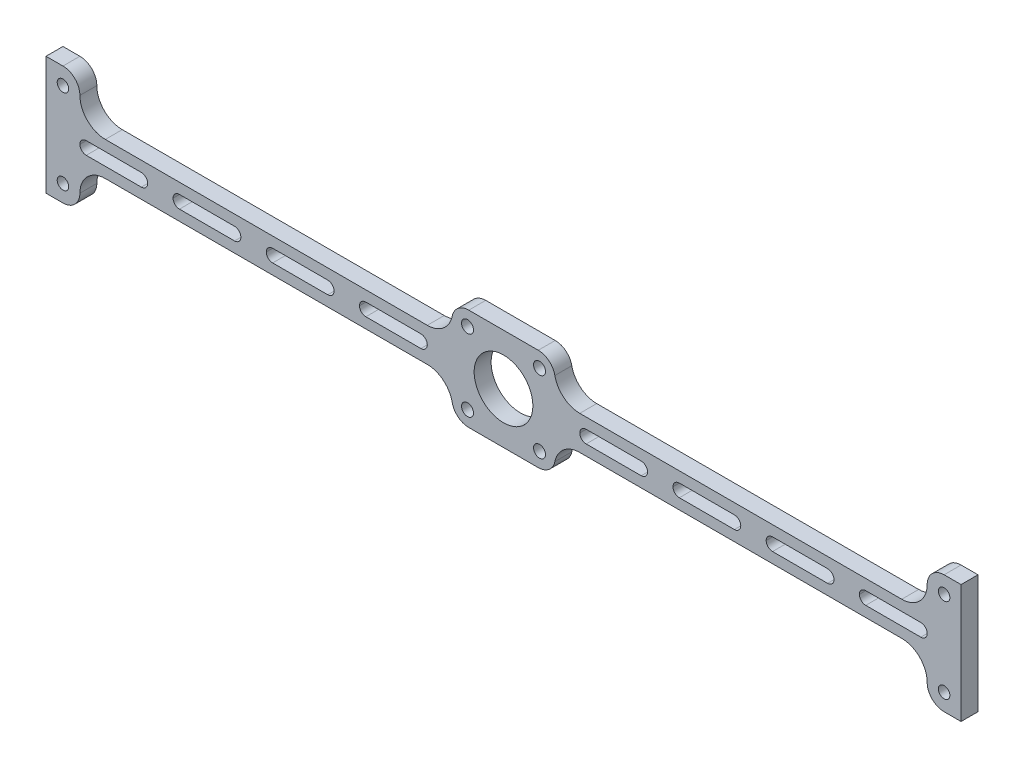
SolidWorks part; units mm, degrees
material "6061-T6 (SS)"
ref_plane "Front" through (0, 0, 0) normal (0, 0, 1) x (1, 0, 0)
ref_plane "Top" through (0, 0, 0) normal (0, 1, 0) x (1, 0, 0)
ref_plane "Right" through (0, 0, 0) normal (1, 0, 0) x (0, 0, -1)
sketch "Sketch4" plane through (0, 0, 0) normal (0, 0, 1) x (1, 0, 0)
  line L0 (-165.1, 0) -> (0, 0) construction
  line L1 (-158.75, -6.35) -> (158.75, -6.35)
  line L2 (-158.75, -6.35) -> (-158.75, 6.35)
  line L3 (-158.75, 6.35) -> (158.75, 6.35)
  line L4 (158.75, -6.35) -> (158.75, 6.35)
  line L5 (-158.75, -6.35) -> (158.75, 6.35) construction
  line L6 (-158.75, 6.35) -> (158.75, -6.35) construction
  line L7 (-171.45, -22.225) -> (-158.75, -22.225)
  line L8 (-171.45, -22.225) -> (-171.45, 22.225)
  line L9 (-171.45, 22.225) -> (-158.75, 22.225)
  line L10 (-158.75, -22.225) -> (-158.75, 22.225)
  line L11 (-171.45, -22.225) -> (-158.75, 22.225) construction
  line L12 (-171.45, 22.225) -> (-158.75, -22.225) construction
  line L17 (171.45, 22.225) -> (158.75, 22.225)
  line L18 (171.45, 22.225) -> (171.45, -22.225)
  line L19 (171.45, -22.225) -> (158.75, -22.225)
  line L20 (158.75, 22.225) -> (158.75, -22.225)
  line L21 (171.45, 22.225) -> (158.75, -22.225) construction
  line L22 (171.45, -22.225) -> (158.75, 22.225) construction
  line L23 (0, 0) -> (165.1, 0) construction
  line L25 (-19.05, 19.05) -> (19.05, 19.05)
  line L26 (-19.05, 19.05) -> (-19.05, -19.05)
  line L27 (-19.05, -19.05) -> (19.05, -19.05)
  line L28 (19.05, 19.05) -> (19.05, -19.05)
  line L29 (-19.05, 19.05) -> (19.05, -19.05) construction
  line L30 (-19.05, -19.05) -> (19.05, 19.05) construction
  point P0 (0, 0)
  point P6 (-165.1, 0)
  point P12 (165.1, 0)
  dimension "D1" = 342.9
  dimension "D2" = 12.7
  dimension "D3" = 44.45
  dimension "D4" = 12.7
  dimension "D5" = 38.1
  dimension "D6" = 38.1
extrude "Boss-Extrude2" add sketch "Sketch4" along normal blind 6.35 contours L7 L10 L2 L9 L8 | L26 L3 L2 L1 | L28 L25 L26 L3 | L28 L3 L26 L1 | L28 L1 L26 L27 | L3 L28 L1 L4 | L17 L20 L4 L19 L18 region at (-88.9, 0, 0) region at (-165.1, 0, 0) region at (0, 0, 0) region at (0, -12.7, 0) region at (88.9, 0, 0) region at (0, 12.7, 0) region at (165.1, 0, 0)
fillet "Fillet4" radius 9.525 8 edges at (158.75, 6.35, 3.175) (158.75, -6.35, 3.175) (-158.75, -6.35, 3.175) (-158.75, 6.35, 3.175) (-19.05, -6.35, 3.175) (-19.05, 6.35, 3.175) (19.05, -6.35, 3.175) (19.05, 6.35, 3.175)
fillet "Fillet5" radius 6.35 8 edges at (-158.75, 22.225, 3.175) (-158.75, -22.225, 3.175) (158.75, -22.225, 3.175) (158.75, 22.225, 3.175) (19.05, 19.05, 3.175) (-19.05, 19.05, 3.175) (-19.05, -19.05, 3.175) (19.05, -19.05, 3.175)
sketch "Sketch5" plane through (0, 0, 6.35) normal (0, 0, 1) x (1, 0, 0)
  line L0 (-165.1, 22.225) -> (-165.1, -22.225) construction
  line L1 (-171.45, 22.225) -> (-165.1, 22.225) construction
  line L2 (-171.45, -22.225) -> (-165.1, -22.225) construction
  line L3 (-171.45, -22.225) -> (-171.45, 22.225) construction
  line L4 (165.1, 22.225) -> (165.1, -22.225) construction
  line L5 (171.45, 22.225) -> (165.1, 22.225) construction
  line L6 (171.45, -22.225) -> (165.1, -22.225) construction
  line L7 (171.45, 22.225) -> (171.45, -22.225) construction
  circle A0 centre (0, 0) radius 11
  circle A2 centre (-165.1, 15.875) radius 2.1527
  circle A3 centre (-165.1, -15.875) radius 2.1527
  circle A5 centre (165.1, 15.875) radius 2.1527
  circle A6 centre (165.1, -15.875) radius 2.1527
  point P19 (165.1, 0)
  point P20 (-165.1, 0)
  dimension "D3" = 22
  dimension "D5" = 31.75
  dimension "D6" = 4.3053
  dimension "D7" = 15.875
  dimension "D8" = 31.75
  dimension "D1" = 6.35
  dimension "D2" = 6.35
  dimension "D4" = 15.875
extrude "Cut-Extrude1" cut sketch "Sketch5" against normal blind 6.35
sketch "Sketch6" plane through (0, 0, 6.35) normal (0, 0, 1) x (1, 0, 0)
  line L1 (-13.4938, -13.4938) -> (13.4937, -13.4938) construction
  line L2 (-13.4938, -13.4938) -> (-13.4938, 13.4937) construction
  line L3 (-13.4938, 13.4937) -> (13.4937, 13.4937) construction
  line L4 (13.4937, -13.4938) -> (13.4937, 13.4937) construction
  line L5 (-13.4938, -13.4938) -> (13.4937, 13.4937) construction
  line L6 (-13.4938, 13.4937) -> (13.4937, -13.4938) construction
  circle A0 centre (-13.4938, -13.4938) radius 2.2479
  circle A1 centre (13.4937, -13.4938) radius 2.2479
  circle A2 centre (13.4937, 13.4937) radius 2.2479
  circle A3 centre (-13.4938, 13.4937) radius 2.2479
  point P0 (0, 0)
  dimension "D3" = 4.4958
  dimension "D2" = 26.9875
extrude "Cut-Extrude2" cut sketch "Sketch6" against normal blind 6.35
sketch "Sketch7" plane through (0, 0, 6.35) normal (0, 0, 1) x (1, 0, 0)
  line L0 (-171.45, 0) -> (171.45, 0) construction
  line L1 (-171.45, -22.225) -> (-171.45, 22.225) construction
  line L2 (171.45, 22.225) -> (171.45, -22.225) construction
  line L4 (-156.369, 2.3812) -> (-135.731, 2.3813)
  line L5 (-158.75, 0.0003) -> (-158.75, -0.0003)
  line L6 (-156.369, -2.3813) -> (-135.731, -2.3812)
  line L7 (-133.35, 0.0003) -> (-133.35, -0.0003)
  line L8 (-158.75, 2.3813) -> (-133.35, -2.3812) construction
  line L9 (-158.75, -2.3813) -> (-133.35, 2.3813) construction
  arc A0 (-135.731, 2.3813) -> (-133.35, 0.0003) centre (-135.731, 0.0003) cw
  arc A1 (-135.731, -2.3812) -> (-133.35, -0.0003) centre (-135.731, -0.0003) ccw
  arc A2 (-158.75, -0.0003) -> (-156.369, -2.3813) centre (-156.369, -0.0003) ccw
  arc A3 (-156.369, 2.3812) -> (-158.75, 0.0003) centre (-156.369, 0.0003) ccw
  point P6 (-146.05, 0)
  dimension "D3" = 2.381
  dimension "D1" = 12.7
  dimension "D2" = 4.7625
  dimension "D4" = 25.4
extrude "Cut-Extrude3" cut sketch "Sketch7" against normal blind 6.35
pattern_linear "LPattern1" count 4 spacing 34.925 along (1, 0, 0) of "Cut-Extrude3"
mirror "Mirror1" about plane through (0, 0, 0) normal (1, 0, 0) of "LPattern1"
